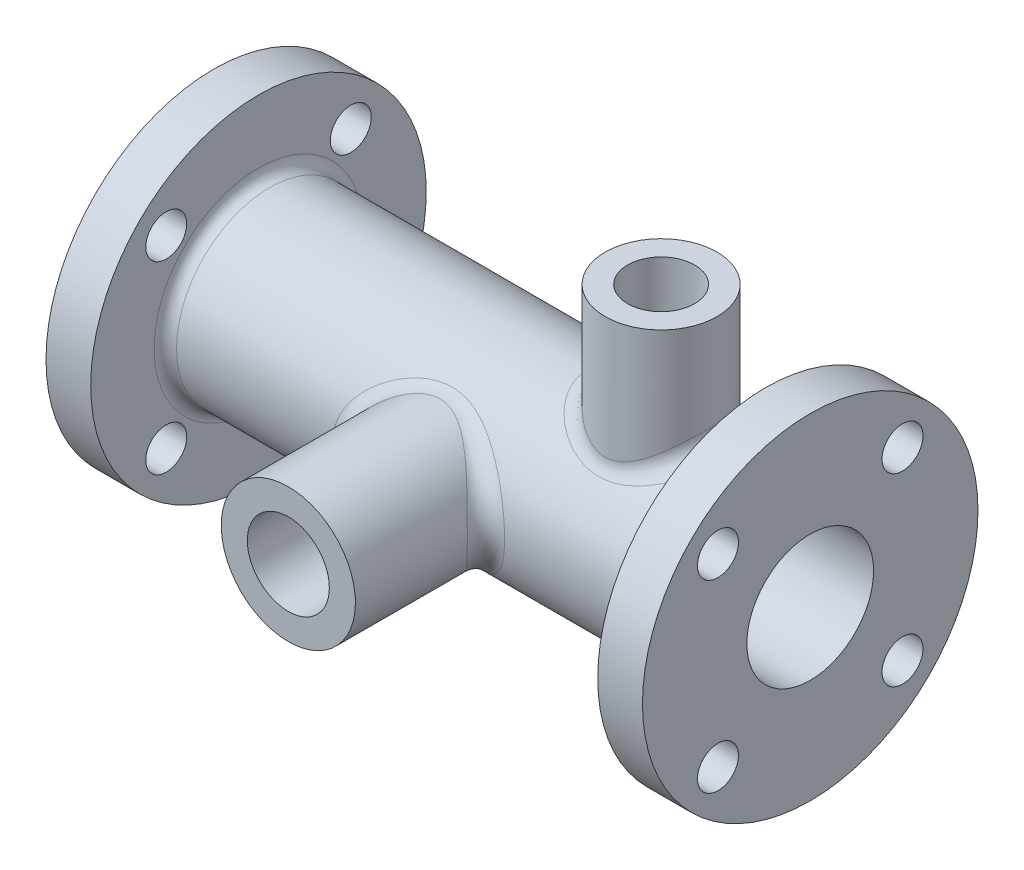
SolidWorks part; units mm, degrees
ref_plane "前视基准面" through (0, 0, 0) normal (0, 0, 1) x (1, 0, 0)
ref_plane "上视基准面" through (0, 0, 0) normal (0, 1, 0) x (1, 0, 0)
ref_plane "右视基准面" through (0, 0, 0) normal (1, 0, 0) x (0, 0, -1)
ref_plane "基准面1" through (-80, 0, 0) normal (1, 0, 0) x (0, 0, -1)
sketch "草图1" plane through (-80, 0, 0) normal (1, 0, 0) x (0, 0, -1)
  circle A0 centre (0, 0) radius 25
extrude "凸台-拉伸1" add sketch "草图1" along normal blind 160
sketch "草图2" plane through (-80, 0, 0) normal (1, 0, 0) x (0, 0, -1)
  circle A0 centre (0, 0) radius 45
extrude "凸台-拉伸2" add sketch "草图2" along normal blind 12
ref_plane "基准面2" through (68, 0, 0) normal (1, 0, 0) x (0, 0, -1)
sketch "草图3" plane through (68, 0, 0) normal (1, 0, 0) x (0, 0, -1)
  circle A0 centre (0, 0) radius 45
extrude "凸台-拉伸3" add sketch "草图3" along normal blind 12
sketch "草图4" plane through (0, 0, 0) normal (0, 0, 1) x (1, 0, 0)
  circle A0 centre (0, 0) radius 18
extrude "凸台-拉伸4" add sketch "草图4" along normal blind 60
sketch "草图5" plane through (0, 0, 0) normal (0, 1, 0) x (1, 0, 0)
  circle A0 centre (40, 0) radius 15
extrude "凸台-拉伸5" add sketch "草图5" along normal blind 55
fillet "圆角1" radius 5 2 edges at (39.9676, 20, 15) (-17.7147, -3.1921, 24.7954)
fillet "圆角2" radius 3 2 edges at (68, 0, -25) (-68, 0, -25)
sketch "草图6" plane through (-80, 0, 0) normal (1, 0, 0) x (0, 0, -1)
  circle A0 centre (0, 0) radius 17
extrude "切除-拉伸1" cut sketch "草图6" along normal through all
ref_plane "基准面3" through (0, 0, 60) normal (0, 0, 1) x (1, 0, 0)
sketch "草图7" plane through (0, 0, 60) normal (0, 0, 1) x (1, 0, 0)
  circle A0 centre (0, 0) radius 11
extrude "切除-拉伸2" cut sketch "草图7" against normal blind 50
ref_plane "基准面4" through (0, 55, 0) normal (0, 1, 0) x (1, 0, 0)
sketch "草图8" plane through (0, 55, 0) normal (0, 1, 0) x (1, 0, 0)
  circle A0 centre (40, 0) radius 9
extrude "切除-拉伸3" cut sketch "草图8" against normal blind 45
sketch "草图9" plane through (-80, 0, 0) normal (1, 0, 0) x (0, 0, -1)
  circle A0 centre (-24.7487, 24.7487) radius 5.5
  circle A1 centre (24.7487, 24.7487) radius 5.5
  circle A2 centre (24.7487, -24.7487) radius 5.5
  circle A3 centre (-24.7487, -24.7487) radius 5.5
extrude "切除-拉伸4" cut sketch "草图9" along normal blind 12
ref_plane "基准面5" through (80, 0, 0) normal (1, 0, 0) x (0, 0, -1)
sketch "草图10" plane through (80, 0, 0) normal (1, 0, 0) x (0, 0, -1)
  circle A0 centre (-24.7487, 24.7487) radius 5.5
  circle A1 centre (24.7487, 24.7487) radius 5.5
  circle A2 centre (24.7487, -24.7487) radius 5.5
  circle A3 centre (-24.7487, -24.7487) radius 5.5
extrude "切除-拉伸5" cut sketch "草图10" against normal blind 12
